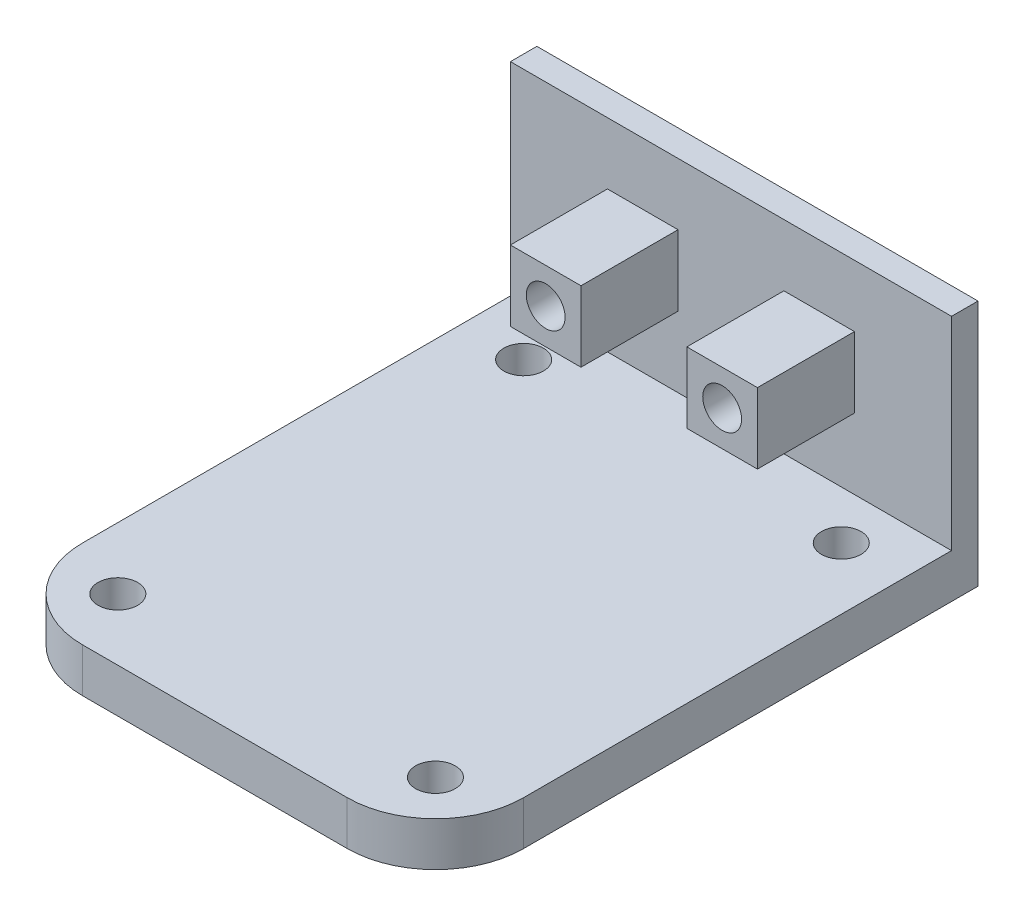
SolidWorks part; units mm, degrees
ref_plane "Front Plane" through (0, 0, 0) normal (0, 0, 1) x (1, 0, 0)
ref_plane "Top Plane" through (0, 0, 0) normal (0, 1, 0) x (1, 0, 0)
ref_plane "Right Plane" through (0, 0, 0) normal (1, 0, 0) x (0, 0, -1)
sketch "Sketch1" plane through (0, 0, 0) normal (0, 0, 1) x (1, 0, 0)
  line L1 (-25, 16.5) -> (25, 16.5)
  line L2 (-25, 16.5) -> (-25, -16.5)
  line L3 (-25, -16.5) -> (25, -16.5)
  line L4 (25, 16.5) -> (25, -16.5)
  line L5 (-25, 16.5) -> (25, -16.5) construction
  line L6 (-25, -16.5) -> (25, 16.5) construction
  point P0 (0, 0)
  dimension "D1" = 33
  dimension "D2" = 50
extrude "Boss-Extrude1" add sketch "Sketch1" along normal blind 3 contours L2 L3 L4 L1
sketch "Sketch2" plane through (0, 0, 3) normal (0, 0, 1) x (1, 0, 0)
  line L0 (25, 16.5) -> (25, -16.5) construction
  line L1 (-25, -16.5) -> (25, -16.5)
  line L2 (-25, -16.5) -> (-25, -11.5)
  line L3 (-25, -11.5) -> (25, -11.5)
  line L4 (25, -16.5) -> (25, -11.5)
  dimension "D1" = 5
extrude "Boss-Extrude2" add sketch "Sketch2" along normal blind 58.5
sketch "Sketch3" plane through (0, -11.5, 0) normal (0, 1, 0) x (1, 0, 0)
  line L0 (-25, -51.5) -> (-25, -61.5)
  line L1 (-25, -61.5) -> (-15, -61.5)
  line L2 (15, -61.5) -> (25, -61.5)
  line L3 (25, -61.5) -> (25, -51.5)
  arc A1 (15, -61.5) -> (25, -51.5) centre (15, -51.5) ccw construction
  arc A2 (15, -61.5) -> (25, -51.5) centre (15, -51.5) ccw
  arc A3 (-25, -51.5) -> (-15, -61.5) centre (-15, -51.5) ccw construction
  arc A4 (-25, -51.5) -> (-15, -61.5) centre (-15, -51.5) ccw
  circle A5 centre (-18, -54.5) radius 2.2479 construction
  circle A6 centre (-18, -54.5) radius 2.2479
  circle A7 centre (18, -54.5) radius 2.2479 construction
  circle A8 centre (18, -54.5) radius 2.2479
  circle A9 centre (-18, -8.5) radius 2.2479 construction
  circle A10 centre (-18, -8.5) radius 2.2479
  circle A11 centre (18, -8.5) radius 2.2479 construction
  circle A12 centre (18, -8.5) radius 2.2479
extrude "Cut-Extrude1" cut sketch "Sketch3" against normal up to surface (5 mm away) up to face at (0, -16.5, 30.75)
sketch "Sketch4" plane through (0, 0, 3) normal (0, 0, 1) x (1, 0, 0)
  line L5 (-14.0006, 4.5) -> (-6.0006, 4.5)
  line L6 (-14.0006, 4.5) -> (-14.0006, -3.5)
  line L7 (-14.0006, -3.5) -> (-6.0006, -3.5)
  line L8 (-6.0006, 4.5) -> (-6.0006, -3.5)
  line L9 (-14.0006, 4.5) -> (-6.0006, -3.5) construction
  line L10 (-14.0006, -3.5) -> (-6.0006, 4.5) construction
  line L11 (5.9994, 4.5) -> (13.9994, 4.5)
  line L12 (5.9994, 4.5) -> (5.9994, -3.5)
  line L13 (5.9994, -3.5) -> (13.9994, -3.5)
  line L14 (13.9994, 4.5) -> (13.9994, -3.5)
  line L15 (5.9994, 4.5) -> (13.9994, -3.5) construction
  line L16 (5.9994, -3.5) -> (13.9994, 4.5) construction
  circle A0 centre (-10.0006, 0.5) radius 2.2 construction
  circle A1 centre (-10.0006, 0.5) radius 2.2
  circle A2 centre (9.9994, 0.5) radius 2.2 construction
  circle A3 centre (9.9994, 0.5) radius 2.2
  dimension "D1" = 8
extrude "Boss-Extrude3" add sketch "Sketch4" along normal blind 11
sketch "Sketch5" plane through (0, 0, 14) normal (0, 0, 1) x (1, 0, 0)
  circle A0 centre (9.9994, 0.5) radius 2.2 construction
  circle A1 centre (9.9994, 0.5) radius 2.2
  circle A2 centre (-10.0006, 0.5) radius 2.2 construction
  circle A3 centre (-10.0006, 0.5) radius 2.2
extrude "Cut-Extrude2" cut sketch "Sketch5" against normal up to surface (14 mm away) up to face at (0, 0, 0)
sketch "Sketch6" plane through (0, 0, 3) normal (0, 0, 1) x (1, 0, 0)
  line L0 (25, 16.5) -> (25, -11.5) construction
  line L1 (-25, 16.5) -> (25, 16.5)
  line L2 (-25, 16.5) -> (-25, 11.5)
  line L3 (-25, 11.5) -> (25, 11.5)
  line L4 (25, 16.5) -> (25, 11.5)
  dimension "D1" = 5
extrude "Cut-Extrude3" cut sketch "Sketch6" against normal up to surface (3 mm away) up to face at (7.7994, 0.5, 0)
